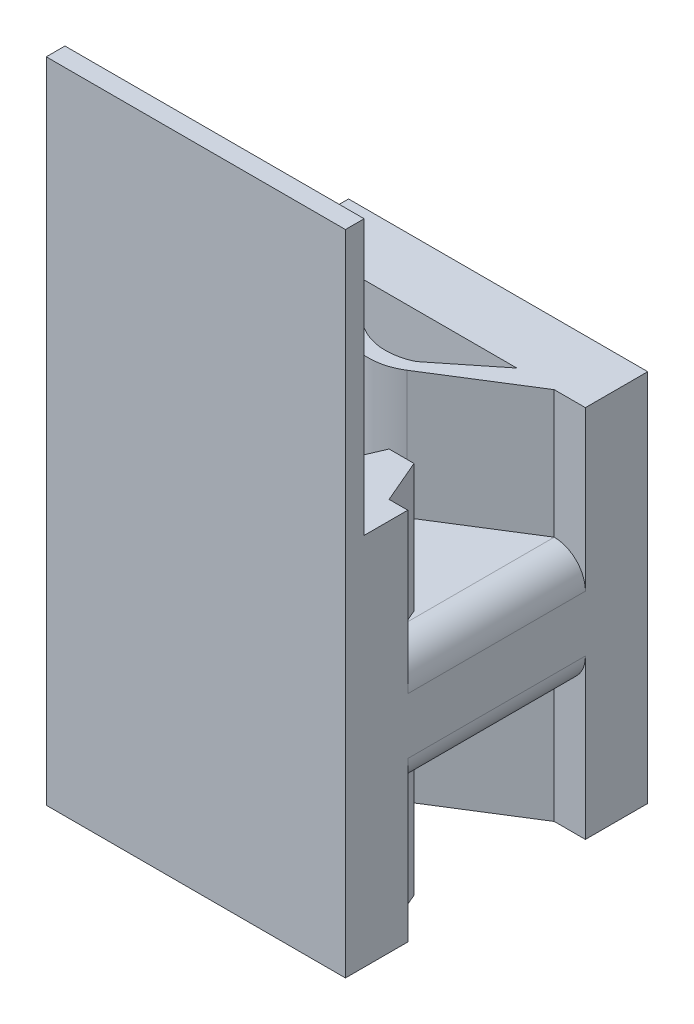
SolidWorks part; units mm, degrees
ref_plane "Front" through (0, 0, 0) normal (0, 0, 1) x (1, 0, 0)
ref_plane "Top" through (0, 0, 0) normal (0, 1, 0) x (1, 0, 0)
ref_plane "Right" through (0, 0, 0) normal (1, 0, 0) x (0, 0, -1)
sketch "Sketch1" plane through (0, 0, 0) normal (0, 1, 0) x (1, 0, 0)
  line L0 (-108.5996, 0) -> (78.4445, 0) construction
  line L1 (-22.9882, 10) -> (-19.9882, 17)
  line L2 (-19.9882, 17) -> (-15.9882, 17)
  line L3 (-15.9882, 17) -> (-12.9882, 10)
  line L4 (-12.9882, 10) -> (-6.9882, 10)
  line L5 (-6.9882, 10) -> (-3.9882, 17)
  line L6 (-3.9882, 17) -> (0.0118, 17)
  line L7 (0.0118, 17) -> (3.0118, 10)
  line L8 (3.0118, 10) -> (9.0118, 10)
  line L9 (9.0118, 10) -> (12.0118, 17)
  line L10 (12.0118, 17) -> (16.0118, 17)
  line L11 (16.0118, 17) -> (19.0118, 10)
  line L12 (19.0118, 10) -> (22.0118, 10)
  line L13 (19.0118, 10) -> (25.0118, 10) [skipped]
  line L14 (-22.9882, 10) -> (-25.9882, 10)
  line L15 (-25.9882, 10) -> (-25.9882, 0)
  line L16 (-25.9882, 0) -> (22.0118, 0)
  line L17 (22.0118, 0) -> (22.0118, 10)
  dimension "D1" = 7
  dimension "D2" = 3
  dimension "D3" = 3
  dimension "D4" = 4
  dimension "D5" = 6
  dimension "D7" = 3
  dimension "D8" = 3
  dimension "D9" = 10
  dimension "D6" = 3
extrude "Boss-Extrude1" add sketch "Sketch1" along normal blind 60
sketch "Sketch2" plane through (0, 0, 0) normal (0, 0, 1) x (1, 0, 0)
  line L0 (-25.9882, 39.5) -> (22.0118, 39.5)
  line L1 (-25.9882, 60) -> (-25.9882, 0) construction
  line L2 (22.0118, 60) -> (22.0118, 0) construction
  line L3 (22.0118, 39.5) -> (22.0118, 20.5)
  line L4 (22.0118, 20.5) -> (-25.9882, 20.5)
  line L5 (-25.9882, 20.5) -> (-25.9882, 39.5)
  line L7 (-25.9882, 30) -> (22.0118, 30) construction
  line L8 (-25.9882, 0) -> (22.0118, 0) construction
  dimension "D1" = 19
  dimension "D2" = 30
extrude "Boss-Extrude2" add sketch "Sketch2" against normal blind 48.5
sketch "Sketch3" plane through (0, 0, 0) normal (0, 1, 0) x (1, 0, 0)
  line L0 (-25.9882, 48.5) -> (22.0118, 48.5)
  line L1 (22.0118, 48.5) -> (22.0118, 38.5)
  line L2 (22.0118, 48.5) -> (22.0118, 10) construction
  line L3 (22.0118, 38.5) -> (-25.9882, 38.5)
  line L4 (-25.9882, 48.5) -> (-25.9882, 10) construction
  line L5 (-25.9882, 38.5) -> (-25.9882, 48.5)
  line L6 (17.0118, 38.5) -> (2.4813, 29.3776)
  line L7 (11.0118, 38.5) -> (2.0257, 31.3251)
  arc A0 (2.0257, 31.3251) -> (-7.5782, 32.384) centre (-1.944, 39.4022) cw
  arc A1 (2.4813, 29.3776) -> (-9.215, 31.2347) centre (-2.3041, 37) cw
  arc A2 (-9.215, 31.2347) -> (-7.5782, 32.384) centre (-8.3966, 31.8093) cw
  dimension "D5" = 9
  dimension "D6" = 2
  dimension "D7" = 1.5
  dimension "D4" = 9
  dimension "D8" = 1
  dimension "D9" = 5
  dimension "D3" = 2
  dimension "D1" = 10
  dimension "D2" = 6
extrude "Boss-Extrude3" add sketch "Sketch3" along normal blind 60 contours A1 L6 L3 L7 A0 | L5 L3 L1 L0 region at (-1.9882, 0, -43.5) region at (14.0118, 0, -38.2158)
fillet "Fillet3" radius 5 4 edges at (-25.9882, 39.5, -24.25) (-25.9882, 20.5, -24.25) (22.0118, 20.5, -24.25) (22.0118, 39.5, -24.25)
sketch "Sketch4" plane through (0, 0, 0) normal (0, 1, 0) x (1, 0, 0)
  line L0 (-25.9882, 3) -> (22.0118, 3)
  line L1 (-25.9882, 10) -> (-25.9882, 0) construction
  line L2 (22.0118, 0) -> (22.0118, 10) construction
  line L3 (22.0118, 3) -> (22.0118, 0)
  line L4 (22.0118, 0) -> (-25.9882, 0)
  line L5 (-25.9882, 0) -> (-25.9882, 3)
  dimension "D1" = 3
extrude "Boss-Extrude4" add sketch "Sketch4" along normal blind 104
ref_point "Point1"
